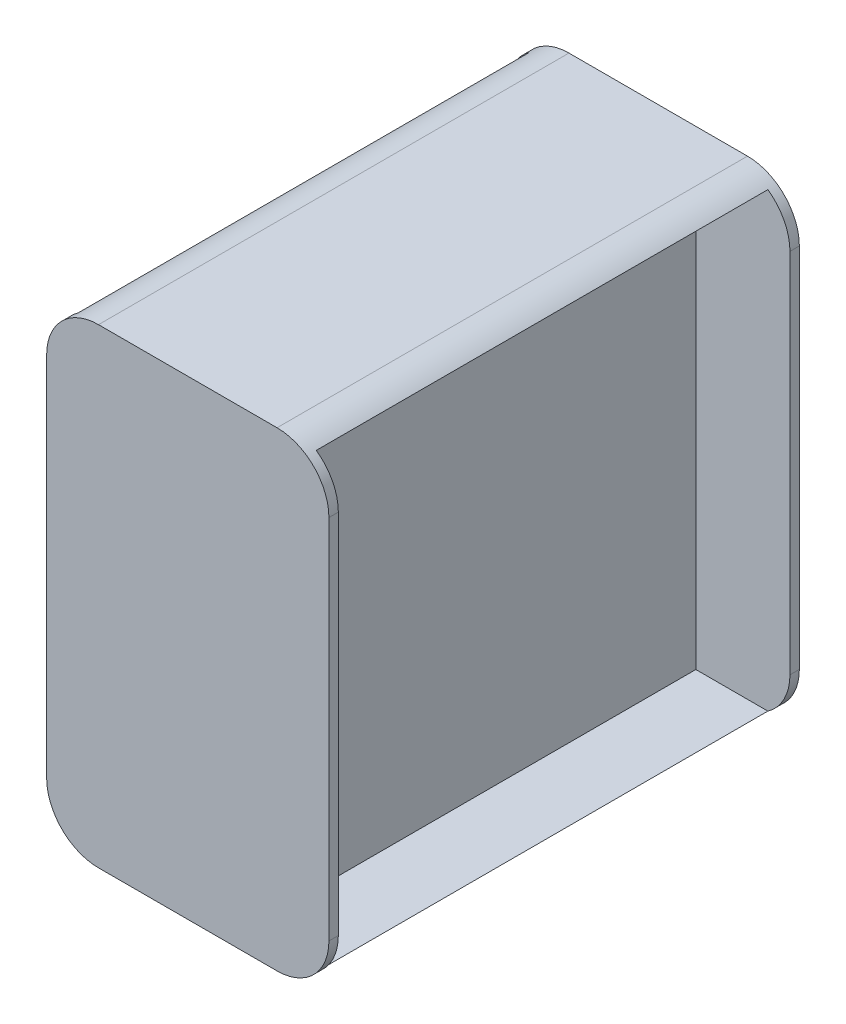
SolidWorks part; units mm, degrees
ref_plane "Front Plane" through (0, 0, 0) normal (0, 0, 1) x (1, 0, 0)
ref_plane "Top Plane" through (0, 0, 0) normal (0, 1, 0) x (1, 0, 0)
ref_plane "Right Plane" through (0, 0, 0) normal (1, 0, 0) x (0, 0, -1)
sketch "Sketch1" plane through (0, 0, 0) normal (0, 1, 0) x (1, 0, 0)
  line L1 (-19.05, 31.75) -> (19.05, 31.75)
  line L2 (-19.05, 31.75) -> (-19.05, -31.75)
  line L3 (-19.05, -31.75) -> (19.05, -31.75)
  line L4 (19.05, 31.75) -> (19.05, -31.75)
  line L5 (-19.05, 31.75) -> (19.05, -31.75) construction
  line L6 (-19.05, -31.75) -> (19.05, 31.75) construction
  point P0 (0, 0)
  dimension "D1" = 38.1
  dimension "D2" = 63.5
extrude "Boss-Extrude1" add sketch "Sketch1" along normal blind 63.5
sketch "Sketch2" plane through (19.05, 0, 0) normal (1, 0, 0) x (0, 0, -1)
  line L0 (-31.75, 63.5) -> (0, 63.5)
  line L1 (-31.75, 63.5) -> (31.75, 63.5) construction
  line L2 (0, 63.5) -> (0, 0) construction
  line L3 (-31.75, 0) -> (31.75, 0) construction
  line L5 (-30.48, 62.23) -> (30.48, 62.23)
  line L6 (-30.48, 62.23) -> (-30.48, 1.27)
  line L7 (-30.48, 1.27) -> (30.48, 1.27)
  line L8 (30.48, 62.23) -> (30.48, 1.27)
  line L9 (-30.48, 62.23) -> (30.48, 1.27) construction
  line L10 (-30.48, 1.27) -> (30.48, 62.23) construction
  point P5 (0, 31.75)
  dimension "D1" = 60.96
  dimension "D2" = 60.96
extrude "Cut-Extrude1" cut sketch "Sketch2" against normal blind 12.7 contours L8 L5 L6 L7 region at (19.05, 31.75, 0)
pattern_linear "LPattern1" count 2 spacing 25.4 along (-1, 0, 0) of "Cut-Extrude1"
fillet "Fillet1" radius 7 2 edges at (19.05, 63.5, 0) (-19.05, 63.5, 0)
fillet "Fillet2" radius 7 2 edges at (-19.05, 0, 0) (19.05, 0, 0)
